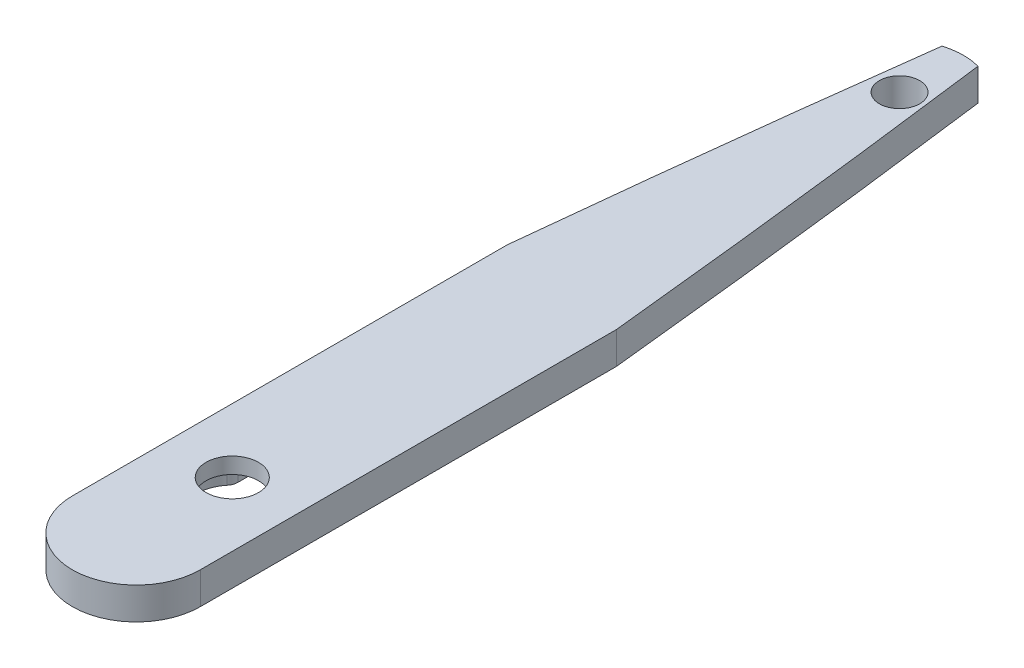
SolidWorks part; units mm, degrees
ref_plane "Front Plane" through (0, 0, 0) normal (0, 0, 1) x (1, 0, 0)
ref_plane "Top Plane" through (0, 0, 0) normal (0, 1, 0) x (1, 0, 0)
ref_plane "Right Plane" through (0, 0, 0) normal (1, 0, 0) x (0, 0, -1)
sketch "Sketch1" plane through (0, 0, 0) normal (0, 1, 0) x (1, 0, 0)
  line L0 (0, 0) -> (0, 12.7862) construction
  line L16 (-23.6152, 0) -> (23.6152, 0) construction
  line L22 (-3.8884, 4.0299) -> (-3.8884, 8.5053)
  line L23 (-3.8177, 9.3432) -> (-2.6646, 16.1267)
  line L24 (3.8299, 9.3786) -> (2.6768, 16.1621)
  line L25 (3.9006, 4.0181) -> (3.9006, 8.5407)
  line L26 (-3.8945, -4.024) -> (-3.8945, -8.5406)
  line L27 (-3.8238, -9.3786) -> (-2.6707, -16.1621)
  line L28 (3.8238, -9.3786) -> (2.6707, -16.1621)
  line L29 (3.8945, -4.024) -> (3.8945, -8.5406)
  line L30 (-10, 104.3) -> (-10, 25)
  line L31 (-7.5, 22.5) -> (7.5, 22.5)
  line L32 (-7.5, 22.5) -> (-7.5, -22.5)
  line L33 (-7.5, -22.5) -> (7.5, -22.5)
  line L34 (7.5, 22.5) -> (7.5, -22.5)
  line L35 (-7.5, 22.5) -> (7.5, -22.5) construction
  line L36 (-7.5, -22.5) -> (7.5, 22.5) construction
  line L41 (-10, 25) -> (10, 25)
  line L42 (-10, 25) -> (-10, -25)
  line L43 (-10, -25) -> (10, -25)
  line L44 (10, 25) -> (10, -25)
  line L45 (-10, 25) -> (10, 25)
  line L46 (-10, 25) -> (-10, 104.3)
  line L48 (10, 25) -> (10, 104.3)
  line L49 (10, 104.3) -> (10, 25)
  arc A8 (-2.5939, 16.9879) -> (2.606, 17) centre (0.006, 17) cw
  arc A9 (-2.6, -17) -> (2.6, -17) centre (0, -17) ccw
  circle A10 centre (0, 0) radius 5.6
  circle A11 centre (0, 0) radius 1.6
  circle A13 centre (0, 0) radius 4.1
  arc A14 (2.6, -17) -> (2.6707, -16.1621) centre (7.6, -17) cw
  arc A15 (-2.6707, -16.1621) -> (-2.6, -17) centre (-7.6, -17) cw
  arc A16 (-3.8945, -8.5406) -> (-3.8238, -9.3786) centre (1.1055, -8.5406) ccw
  arc A17 (3.8238, -9.3786) -> (3.8945, -8.5406) centre (-1.1055, -8.5406) ccw
  arc A18 (2.606, 17) -> (2.6768, 16.1621) centre (7.606, 17) ccw
  arc A19 (-2.6646, 16.1267) -> (-2.5939, 16.9879) centre (-7.5939, 16.9647) ccw
  arc A20 (3.8299, 9.3786) -> (3.9006, 8.5407) centre (-1.0994, 8.5407) cw
  arc A21 (-3.8884, 8.5053) -> (-3.8177, 9.3432) centre (1.1116, 8.5053) cw
  circle A22 centre (0, 104.3) radius 3.15
  arc A23 (-10, 104.3) -> (10, 104.3) centre (0, 104.3) cw
  point P14 (0, 0)
  point P49 (0, 19.6)
  point P50 (0, -19.6)
  dimension "D1" = 11.2
  dimension "D2" = 3.2
  dimension "D7" = 50
  dimension "D3" = 15
  dimension "D4" = 8.2
  dimension "D8" = 5
  dimension "D12" = 6.3
  dimension "D14" = 10
  dimension "D5" = 45
  dimension "D6" = 20
  dimension "D9" = 19.6
  dimension "D10" = 19.6
  dimension "D11" = 2.5
  dimension "D13" = 104.3
extrude "Boss-Extrude1" add sketch "Sketch1" against normal blind 2.2 contours L34 L31 L32 L33 A10 L29 L28 A9 L27 L26 L22 L23 A8 L24 L25 region at (0, 0, -22.0257)
extrude "Boss-Extrude2" add sketch "Sketch1<3>" against normal blind 2.5 contours L44 L41 L42 L43 L31 L34 L33 L32 | L34 L31 L32 L33 L22 A21 L23 A19 A8 A18 L24 A20 L25 A10 L29 A17 L28 A14 A9 A15 L27 A16 L26 region at (0, 0, -24.4615) region at (0, 0, -22.0257)
sketch "Sketch1<3>" plane through (0, 0, 0) normal (0, 1, 0) x (1, 0, 0) same geometry as "Sketch1"
extrude "Boss-Extrude3" add sketch "Sketch1<4>" along normal blind 2.5 contours L34 L31 L32 L33 A10 L29 L28 A9 L27 L26 L22 L23 A8 L24 L25 | A10 L25 L24 A8 L23 L22 | A10 L26 L27 A9 L28 L29 | L44 L41 L42 L43 L31 L34 L33 L32 | A10 A13 region at (0.0082, 0, -11.4698) region at (0.0082, 0, -5.4416) region at (0, 0, 11.4704) region at (0, 0, -24.4615) region at (0, 0, -22.0257)
sketch "Sketch1<4>" plane through (0, 0, 0) normal (0, 1, 0) x (1, 0, 0) same geometry as "Sketch1"
fillet "Fillet1" radius 2 4 edges at (3.8945, -1.25, 4.024) (-3.8945, -1.25, 4.024) (-3.8884, -1.25, -4.0299) (3.9006, -1.25, -4.0181)
extrude "Boss-Extrude4" add sketch "Sketch1<5>" along normal mid plane 5 contours A23 L30 L41 L48 A22 region at (0, 0, -67.9556)
sketch "Sketch1<5>" plane through (0, 0, 0) normal (0, 1, 0) x (1, 0, 0) same geometry as "Sketch1"
fillet "Fillet2" radius 10 2 edges at (10, 0, 25) (-10, 0, 25)
sketch "Sketch2" plane through (0, -2.5, 0) normal (0, -1, 0) x (1, 0, 0)
  line L18 (5.7735, -72.7449) -> (-2.8868, -67.7449)
  line L19 (5.9735, -72.7449) -> (-2.9868, -67.5717)
  line L20 (-2.8868, -77.7449) -> (5.7735, -72.7449)
  line L21 (-2.9868, -77.9181) -> (5.9735, -72.7449)
  line L22 (-2.8868, -67.7449) -> (-2.8868, -77.7449)
  line L23 (-2.9868, -67.5717) -> (-2.9868, -77.9181)
  line L24 (5.7735, -56.7449) -> (-2.8868, -51.7449)
  line L25 (5.9735, -56.7449) -> (-2.9868, -51.5717)
  line L26 (-2.8868, -61.7449) -> (5.7735, -56.7449)
  line L27 (-2.9868, -61.9181) -> (5.9735, -56.7449)
  line L28 (-2.8868, -51.7449) -> (-2.8868, -61.7449)
  line L29 (-2.9868, -51.5717) -> (-2.9868, -61.9181)
  line L30 (5.7735, -40.7449) -> (-2.8868, -35.7449)
  line L31 (5.9735, -40.7449) -> (-2.9868, -35.5717)
  line L32 (-2.8868, -45.7449) -> (5.7735, -40.7449)
  line L33 (-2.9868, -45.9181) -> (5.9735, -40.7449)
  line L34 (-2.8868, -35.7449) -> (-2.8868, -45.7449)
  line L35 (-2.9868, -35.5717) -> (-2.9868, -45.9181)
  line L36 (5.7735, -24.7449) -> (-2.8868, -19.7449)
  line L37 (5.9735, -24.7449) -> (-2.9868, -19.5717)
  line L38 (-2.8868, -29.7449) -> (5.7735, -24.7449)
  line L39 (-2.9868, -29.9181) -> (5.9735, -24.7449)
  line L40 (-2.8868, -19.7449) -> (-2.8868, -29.7449)
  line L41 (-2.9868, -19.5717) -> (-2.9868, -29.9181)
  line L42 (-3.0868, -64.7449) -> (5.8735, -59.5717)
  line L43 (5.8735, -59.5717) -> (5.8735, -69.9181)
  line L44 (5.8735, -69.9181) -> (-3.0868, -64.7449)
  line L45 (5.7735, -69.7449) -> (-2.8868, -64.7449)
  line L46 (-2.8868, -64.7449) -> (5.7735, -59.7449)
  line L47 (5.7735, -59.7449) -> (5.7735, -69.7449)
  line L48 (-3.0868, -48.7449) -> (5.8735, -43.5717)
  line L49 (5.8735, -43.5717) -> (5.8735, -53.9181)
  line L50 (5.8735, -53.9181) -> (-3.0868, -48.7449)
  line L51 (5.7735, -53.7449) -> (-2.8868, -48.7449)
  line L52 (-2.8868, -48.7449) -> (5.7735, -43.7449)
  line L53 (5.7735, -43.7449) -> (5.7735, -53.7449)
  line L54 (-3.0868, -32.7449) -> (5.8735, -27.5717)
  line L55 (5.8735, -27.5717) -> (5.8735, -37.9181)
  line L56 (5.8735, -37.9181) -> (-3.0868, -32.7449)
  line L57 (5.7735, -37.7449) -> (-2.8868, -32.7449)
  line L58 (-2.8868, -32.7449) -> (5.7735, -27.7449)
  line L59 (5.7735, -27.7449) -> (5.7735, -37.7449)
  circle A0 centre (0, -104.3) radius 3.15 construction
  circle A1 centre (0, -104.3) radius 3.15
  point P12 (0, -88.7449)
extrude "Cut-Extrude1" cut sketch "Sketch2" against normal blind 4
sketch "Sketch3" plane through (0, -2.5, 0) normal (0, -1, 0) x (1, 0, 0)
  line L12 (10, -104.3) -> (10, 15)
  line L16 (-10, 15) -> (-10, -104.3)
  line L18 (10, -50.0396) -> (10, 15)
  line L19 (-10, 15) -> (-10, -52.9851)
  arc A43 (10, 15) -> (0, 25) centre (0, 15) ccw
  arc A44 (0, 25) -> (-10, 15) centre (0, 15) ccw
  arc A45 (-10, -104.3) -> (10, -104.3) centre (0, -104.3) ccw
  arc A46 (10, 15) -> (0, 25) centre (0, 15) ccw
  arc A47 (0, 25) -> (-10, 15) centre (0, 15) ccw
  arc A48 (-2.9238, -113.863) -> (2.6121, -113.9528) centre (0, -104.3) ccw
  spline S1 degree 3 poles (2.6121, -113.9528) (2.808, -112.4539) (3.2846, -108.7742) (4.059, -102.6638) (4.9572, -95.3873) (5.9128, -87.4091) (6.9142, -78.7783) (7.9479, -69.5481) (8.9874, -59.9025) (9.6662, -53.3384) (10, -50.0396) knots 0.029046 0.029046 0.029046 0.029046 0.03646 0.047243 0.059254 0.072417 0.086651 0.101866 0.117969 0.134231 0.134231 0.134231 0.134231
  spline S3 degree 3 poles (-10, -52.9851) (-9.7625, -55.3018) (-9.1816, -60.8837) (-8.2479, -69.5481) (-7.2142, -78.7783) (-6.2128, -87.4091) (-5.2572, -95.3873) (-4.359, -102.6638) (-3.5884, -108.7443) (-3.1157, -112.394) (-2.9238, -113.863) knots 0.87061 0.87061 0.87061 0.87061 0.882031 0.898134 0.913349 0.927583 0.940746 0.952757 0.96354 0.970806 0.970806 0.970806 0.970806
  dimension "D1" = 0
extrude "Cut-Extrude2" cut sketch "Sketch3" against normal through all flip side to cut
